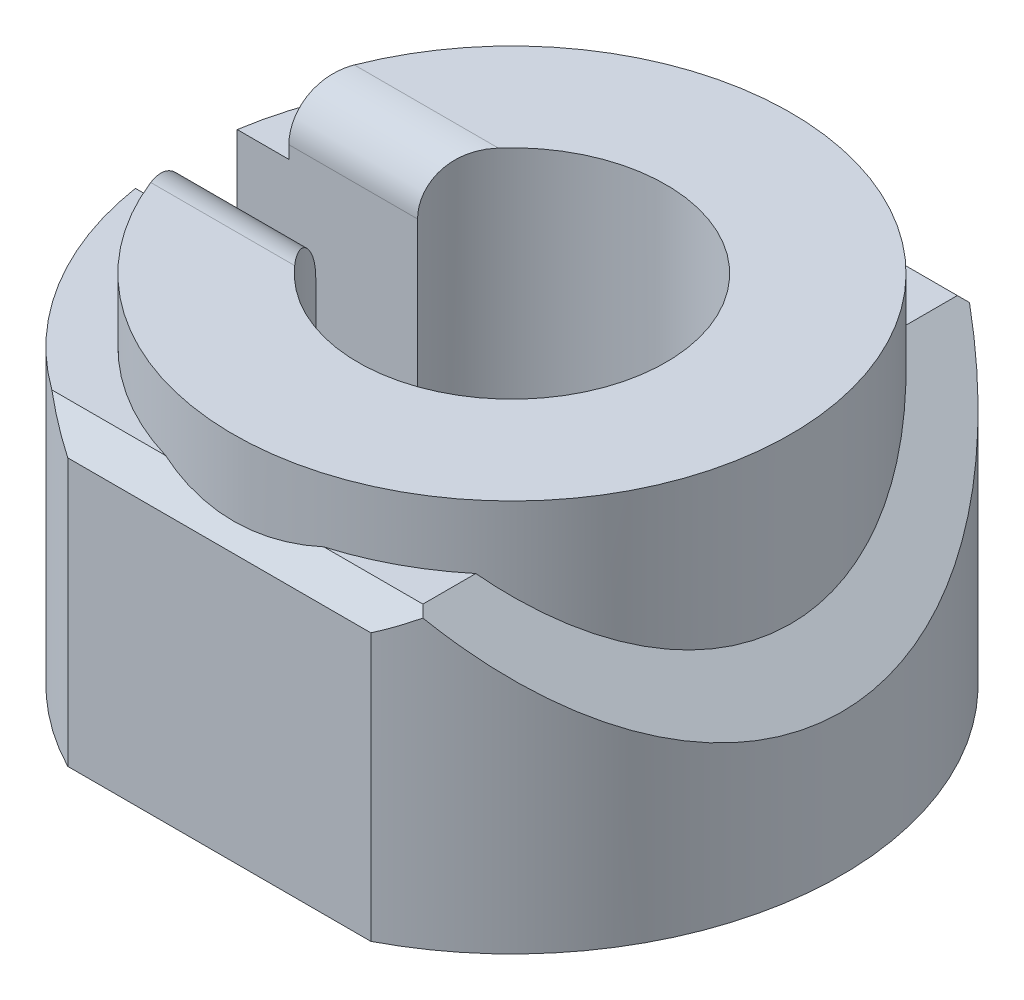
SolidWorks part; units mm, degrees
ref_plane "Front Plane" through (0, 0, 0) normal (0, 0, 1) x (1, 0, 0)
ref_plane "Top Plane" through (0, 0, 0) normal (0, 1, 0) x (1, 0, 0)
ref_plane "Right Plane" through (0, 0, 0) normal (1, 0, 0) x (0, 0, -1)
sketch "Sketch1" plane through (0, 0, 0) normal (0, 1, 0) x (1, 0, 0)
  circle A0 centre (0, 0) radius 6.05
  circle A1 centre (0, 0) radius 10.95
  dimension "D1" = 12.1
  dimension "D2" = 21.9
extrude "Boss-Extrude1" add sketch "Sketch1" against normal blind 2 contours A1 A0 | A0 | A0 | A1 region at (0, 0, 0) region at (-10.6403, 0, 0)
extrude "Boss-Extrude2" add sketch "Sketch1<3>" along normal blind 12
sketch "Sketch1<3>" plane through (0, 0, 0) normal (0, 1, 0) x (1, 0, 0) same geometry as "Sketch1"
sketch "Sketch2" plane through (0, 12, 0) normal (0, 1, 0) x (1, 0, 0)
  circle A0 centre (0, 0) radius 10.95
  circle A1 centre (0, 0) radius 12.95
  circle A2 centre (0, 0) radius 10.95 construction
  dimension "D1" = 2
extrude "Boss-Extrude3" add sketch "Sketch2" against normal up to surface (14 mm away) from offset 2.5 up to face at (0, -2, 10.95) offset against normal yes
sketch "Sketch3" plane through (0, 0, 0) normal (0, 1, 0) x (1, 0, 0)
  line L0 (-50, 11.5) -> (-50, 34.5)
  line L1 (-50, -11.5) -> (50, -11.5)
  line L2 (-50, -11.5) -> (-50, 11.5)
  line L3 (-50, 11.5) -> (50, 11.5)
  line L4 (50, -11.5) -> (50, 11.5)
  line L5 (-50, -11.5) -> (50, 11.5) construction
  line L6 (-50, 11.5) -> (50, -11.5) construction
  line L7 (-50, 11.5) -> (50, 11.5)
  line L8 (-50, 34.5) -> (50, 34.5)
  line L9 (50, 11.5) -> (50, 34.5)
  line L10 (50, -11.5) -> (-50, -11.5)
  line L11 (50, -11.5) -> (50, -34.5)
  line L12 (-50, -11.5) -> (-50, -34.5)
  line L13 (50, -34.5) -> (-50, -34.5)
  point P0 (0, 0)
  dimension "D1" = 23
  dimension "D2" = 100
extrude "Cut-Extrude1" cut sketch "Sketch3" against normal through all both and the other way through all contours L13 L11 L1 L12 | L3 L9 L8 L0 | L0 L7 L9 L8 region at (0, 0, -23) region at (0, 0, 23)
sketch "Sketch4" plane through (0, 0, 0) normal (0, 0, 1) x (1, 0, 0)
  line L0 (4.5, 12) -> (13, 3.5)
  line L1 (0, 0) -> (13, 0)
  line L2 (0, 0) -> (0, 12)
  line L3 (0, 12) -> (13, 12)
  line L4 (13, 0) -> (13, 12)
  line L5 (13, 3.5) -> (4.5, 3.5)
  line L6 (13, 3.5) -> (13, 12)
  line L7 (13, 12) -> (4.5, 12)
  line L8 (4.5, 3.5) -> (4.5, 12)
  dimension "D1" = 13
  dimension "D2" = 12
  dimension "D3" = 4.5
extrude "Cut-Extrude3" cut sketch "Sketch4" against normal through all both and the other way through all contours L0 L4 L3 region at (10.1667, 9.1667, 0)
extrude "Boss-Extrude4" add sketch "Sketch1<5>" along normal up to surface (12 mm away) up to face at (-2, 12, 0)
sketch "Sketch1<5>" plane through (0, 0, 0) normal (0, 1, 0) x (1, 0, 0) same geometry as "Sketch1"
sketch "Sketch5" plane through (0, 0, 0) normal (0, 1, 0) x (1, 0, 0)
  line L0 (-2, -2) -> (-2, 2)
  line L1 (2, 2) -> (-2, 2)
  line L2 (2, 2) -> (2, -2)
  line L3 (2, -2) -> (-2, -2)
  line L4 (-2, 2) -> (-2, -2)
  line L5 (2, 2) -> (-2, -2) construction
  line L6 (2, -2) -> (-2, 2) construction
  line L7 (-2, -2) -> (-20, -2)
  line L8 (-2, 2) -> (-20, 2)
  line L9 (-20, -2) -> (-20, 2)
  point P0 (0, 0)
  dimension "D1" = 4
  dimension "D2" = 20
extrude "Cut-Extrude4" cut sketch "Sketch5" along normal through all contours L9 L7 L0 L8 region at (-11, 0, 0)
fillet "Fillet1" radius 2 4 edges at (-8.2378, 12, 2) (-8.2378, 12, -2) (-9.2522, 0, -2) (-9.2522, 0, 2)
sketch "Sketch6" plane through (0, 0, 0) normal (0, 1, 0) x (1, 0, 0)
  circle A0 centre (0, 0) radius 1.6
  dimension "D1" = 3.2
extrude "Cut-Extrude5" cut sketch "Sketch6" against normal through all both and the other way through all
chamfer "Chamfer1" distance 1 angle 45 2 edges at (0, 9.5, 11.5) (0, 9.5, -11.5)
